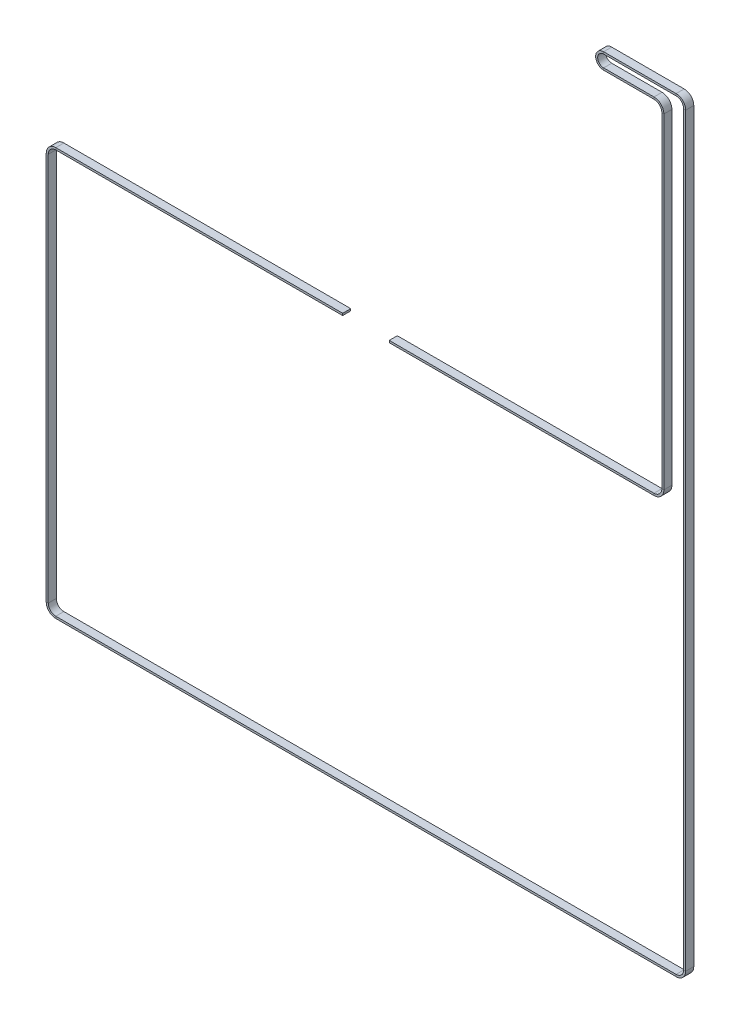
SolidWorks part; units mm, degrees
ref_plane "Front" through (0, 0, 0) normal (0, 0, 1) x (1, 0, 0)
ref_plane "Top" through (0, 0, 0) normal (0, 1, 0) x (1, 0, 0)
ref_plane "Right" through (0, 0, 0) normal (1, 0, 0) x (0, 0, -1)
sketch "Sketch1" plane through (0, 0, 2.2) normal (0, 0, 1) x (1, 0, 0)
  line L0 (377.3122, -142.2854) -> (431.3122, -142.2854)
  line L1 (377.3122, -152.6854) -> (414.8122, -152.6854)
  line L2 (421.4122, -159.2854) -> (421.4122, -401.6854)
  line L3 (437.6872, -148.6604) -> (437.6872, -703.9854)
  line L4 (-37.0628, -703.9854) -> (-37.0628, -414.5104)
  line L5 (431.3122, -710.3604) -> (-30.6878, -710.3604)
  line L6 (-30.6878, -408.1354) -> (182.9622, -408.1354)
  line L9 (414.8122, -408.2854) -> (217.6622, -408.2854)
  line L10 (217.6622, -406.6854) -> (217.6622, -411.6854) construction
  line L12 (182.9622, -411.6854) -> (182.9622, -406.6854) construction
  circle A0 centre (414.8122, -159.2854) radius 6.6 construction
  circle A1 centre (431.3122, -148.6604) radius 6.375 construction
  circle A2 centre (377.3122, -147.4854) radius 5.2 construction
  arc A3 (431.3122, -142.2854) -> (437.6872, -148.6604) centre (431.3122, -148.6604) cw
  arc A4 (377.3122, -152.6854) -> (377.3122, -142.2854) centre (377.3122, -147.4854) cw
  arc A5 (414.8122, -152.6854) -> (421.4122, -159.2854) centre (414.8122, -159.2854) cw
  circle A6 centre (-30.6878, -703.9854) radius 6.375 construction
  arc A7 (-30.6878, -710.3604) -> (-37.0628, -703.9854) centre (-30.6878, -703.9854) cw
  circle A8 centre (431.3122, -148.6604) radius 9 construction
  circle A9 centre (414.8122, -159.2854) radius 9 construction
  circle A10 centre (-30.6878, -414.5104) radius 6.375 construction
  circle A11 centre (431.3122, -703.9854) radius 6.375 construction
  arc A12 (437.6872, -703.9854) -> (431.3122, -710.3604) centre (431.3122, -703.9854) cw
  arc A13 (-37.0628, -414.5104) -> (-30.6878, -408.1354) centre (-30.6878, -414.5104) cw
  circle A14 centre (414.8122, -401.6854) radius 6.6 construction
  arc A15 (421.4122, -401.6854) -> (414.8122, -408.2854) centre (414.8122, -401.6854) cw
  circle A16 centre (414.8122, -401.6854) radius 5.9875 construction
  circle A17 centre (-30.6878, -414.5104) radius 5.9875 construction
  dimension "D1" = 12.75
ref_plane "Plane1" through (182.9622, -408.1354, 2.2) normal (1, 0, 0) x (0, 0, -1)
sketch "Sketch4" plane through (182.9622, -408.1354, 2.2) normal (1, 0, 0) x (0, 0, -1)
  line L0 (0, 259.475) -> (0, -295.85) construction
  line L1 (3, -0.75) -> (-3, -0.75)
  line L2 (3, -0.75) -> (3, 0.75)
  line L3 (3, 0.75) -> (-3, 0.75)
  line L4 (-3, -0.75) -> (-3, 0.75)
  line L5 (3, -0.75) -> (-3, 0.75) construction
  line L6 (3, 0.75) -> (-3, -0.75) construction
  line L7 (0, 0) -> (0, -12.75) construction
  point P0 (0, 0)
  dimension "D1" = 1.5
  dimension "D2" = 6
sweep "Sweep1" add profiles "Sketch4" path "Sketch1"
